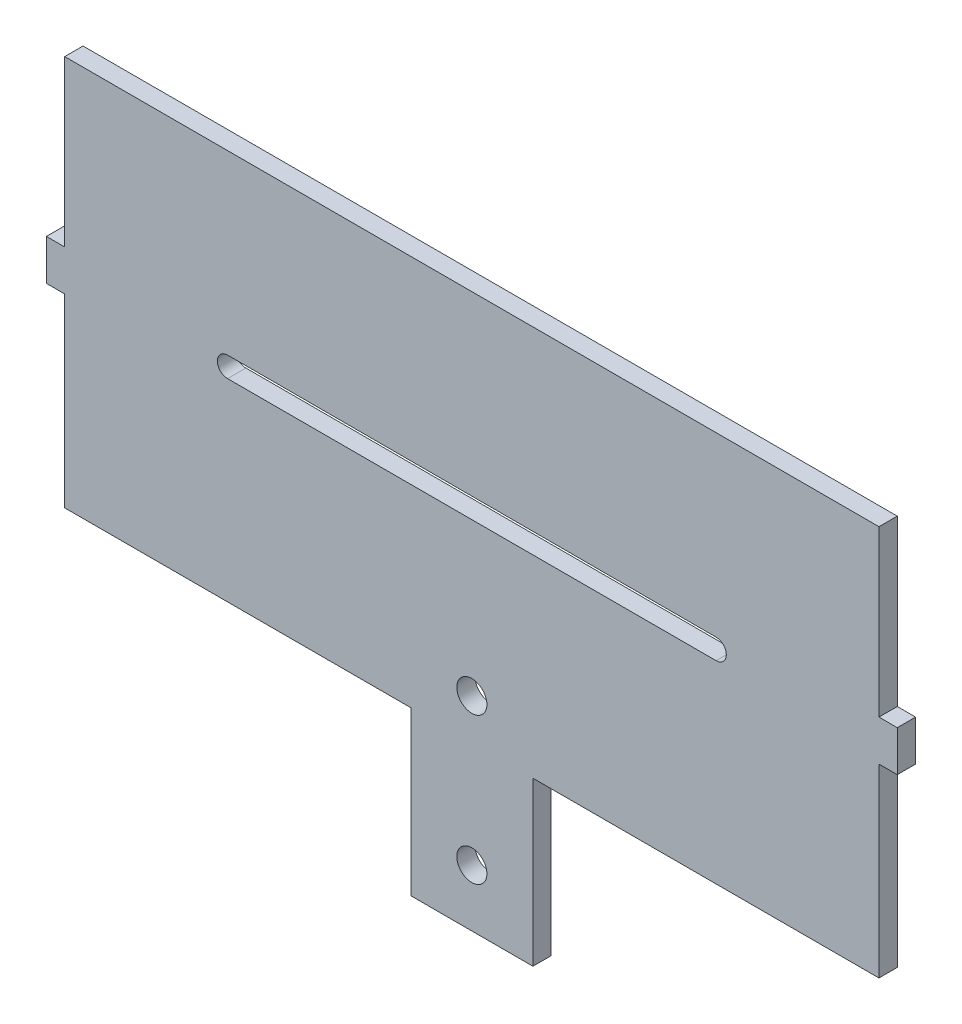
SolidWorks part; units mm, degrees
ref_plane "Front Plane" through (0, 0, 0) normal (0, 0, 1) x (1, 0, 0)
ref_plane "Top Plane" through (0, 0, 0) normal (0, 1, 0) x (1, 0, 0)
ref_plane "Right Plane" through (0, 0, 0) normal (1, 0, 0) x (0, 0, -1)
sketch "Sketch1" plane through (0, 0, 0) normal (0, 0, 1) x (1, 0, 0)
  line L0 (19.05, -63.5) -> (127, -63.5)
  line L1 (-127, -63.5) -> (-19.05, -63.5)
  line L2 (-127, -63.5) -> (-127, -5.715)
  line L3 (-127, 63.5) -> (127, 63.5)
  line L4 (127, -63.5) -> (127, -5.715)
  line L5 (-127, -63.5) -> (127, 63.5) construction
  line L6 (-127, 63.5) -> (127, -63.5) construction
  line L11 (-127, 6.985) -> (-127, 63.5)
  line L12 (-132.715, -5.715) -> (-127, -5.715)
  line L13 (-132.715, -5.715) -> (-132.715, 6.985)
  line L14 (-132.715, 6.985) -> (-127, 6.985)
  line L16 (0, -55) -> (0, 55) construction
  line L17 (132.715, -5.715) -> (127, -5.715)
  line L18 (132.715, -5.715) -> (132.715, 6.985)
  line L19 (132.715, 6.985) -> (127, 6.985)
  line L20 (127, 6.985) -> (127, 63.5)
  line L22 (-19.05, -114.3) -> (19.05, -114.3)
  line L23 (-19.05, -114.3) -> (-19.05, -63.5)
  line L25 (19.05, -114.3) -> (19.05, -63.5)
  point P0 (0, 0)
  point P6 (0, -63.5)
  point P9 (0, -63.5)
  point P10 (-127, 0)
  dimension "D1" = 127
  dimension "D2" = 254
  dimension "D3" = 38.1
  dimension "D4" = 50.8
  dimension "D5" = 12.7
  dimension "D6" = 57.785
extrude "Boss-Extrude1" add sketch "Sketch1" along normal blind 5.715
sketch "Sketch2" plane through (0, 0, 5.715) normal (0, 0, 1) x (1, 0, 0)
  line L0 (76.2, 0) -> (-76.2, 0) construction
  line L1 (76.2, -3.175) -> (-76.2, -3.175)
  line L2 (76.2, 3.175) -> (-76.2, 3.175)
  arc A0 (76.2, -3.175) -> (76.2, 3.175) centre (76.2, 0) ccw
  arc A1 (-76.2, 3.175) -> (-76.2, -3.175) centre (-76.2, 0) ccw
  point P3 (0, 0)
  dimension "D1" = 152.4
  dimension "D2" = 6.35
extrude "Cut-Extrude1" cut sketch "Sketch2" against normal through all
sketch "Sketch4" plane through (0, 0, 5.715) normal (0, 0, 1) x (1, 0, 0)
  line L0 (19.05, -63.5) -> (127, -63.5) construction
  circle A0 centre (0, -50.8) radius 4.699
  dimension "D1" = 9.398
  dimension "D2" = 12.7
extrude "Cut-Extrude2" cut sketch "Sketch4" against normal through all both
sketch "Sketch5" plane through (0, 0, 5.715) normal (0, 0, 1) x (1, 0, 0)
  line L0 (-127, 58.42) -> (127, 58.42)
  line L1 (-127, 63.5) -> (-127, 6.985) construction
  line L2 (127, 6.985) -> (127, 63.5) construction
  line L3 (127, 63.5) -> (-127, 63.5) construction
  line L4 (-127, 58.42) -> (-127, 63.5)
  line L5 (-127, 63.5) -> (127, 63.5)
  line L6 (127, 63.5) -> (127, 58.42)
  dimension "D1" = 5.08
extrude "Cut-Extrude3" cut sketch "Sketch5" against normal through all
sketch "Sketch6" plane through (0, 0, 5.715) normal (0, 0, 1) x (1, 0, 0)
  line L1 (-127, -63.5) -> (-19.05, -63.5) construction
  circle A0 centre (0, -96.52) radius 4.699
  dimension "D1" = 9.398
  dimension "D3" = 33.02
extrude "Cut-Extrude4" cut sketch "Sketch6" against normal through all
